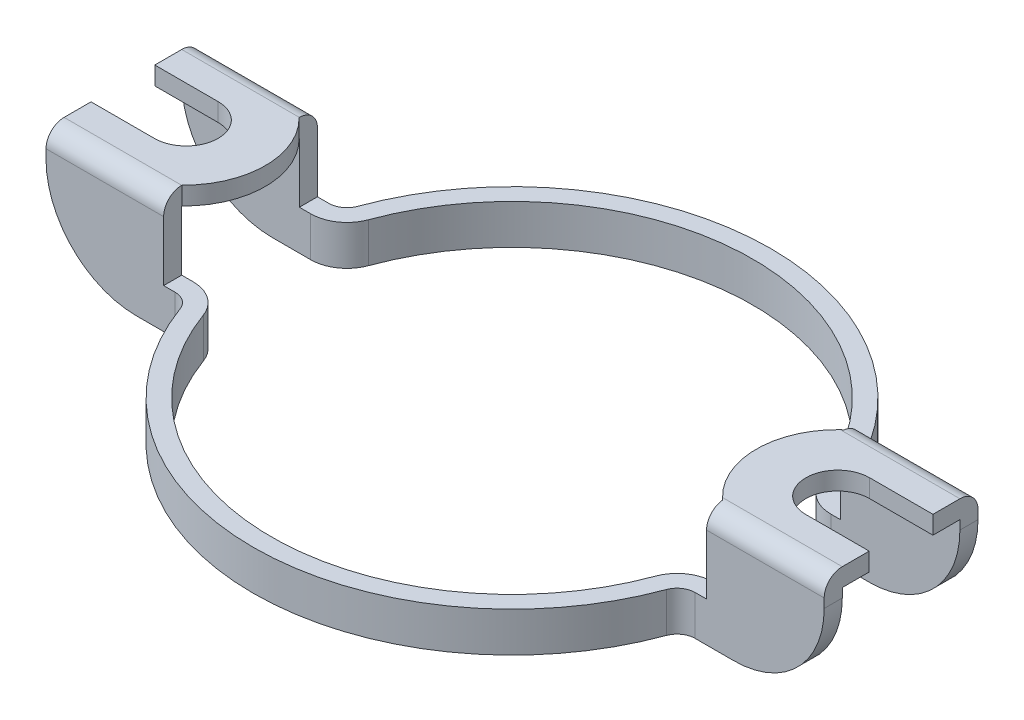
SolidWorks part; units mm, degrees
material "Brass"
ref_plane "Front Plane" through (0, 0, 0) normal (0, 0, 1) x (1, 0, 0)
ref_plane "Top Plane" through (0, 0, 0) normal (0, 1, 0) x (1, 0, 0)
ref_plane "Right Plane" through (0, 0, 0) normal (1, 0, 0) x (0, 0, -1)
sketch "Sketch1" plane through (0, 0, 0) normal (0, 1, 0) x (1, 0, 0)
  line L0 (0, -55) -> (0, 55) construction
  line L1 (-21.5, 4.25) -> (-14.3711, 4.25)
  line L2 (-21.5, 4.25) -> (-21.5, -4.25)
  line L3 (-21.5, -4.25) -> (-14.3711, -4.25)
  line L4 (21.5, 4.25) -> (21.5, -4.25)
  line L5 (-55, 0) -> (55, 0) construction
  line L6 (14.3711, 4.25) -> (21.5, 4.25)
  line L7 (14.3711, -4.25) -> (21.5, -4.25)
  arc A0 (13.4318, 4.9069) -> (-13.4318, 4.9069) centre (0, 0) ccw
  arc A1 (-13.4318, -4.9069) -> (13.4318, -4.9069) centre (0, 0) ccw
  arc A2 (-13.4318, 4.9069) -> (-14.3711, 4.25) centre (-14.3711, 5.25) cw
  arc A3 (14.3711, 4.25) -> (13.4318, 4.9069) centre (14.3711, 5.25) cw
  arc A4 (13.4318, -4.9069) -> (14.3711, -4.25) centre (14.3711, -5.25) cw
  arc A5 (-14.3711, -4.25) -> (-13.4318, -4.9069) centre (-14.3711, -5.25) cw
  point P20 (13.6538, -4.25)
  point P23 (-13.6538, -4.25)
  dimension "D1" = 28.6
  dimension "D6" = 1
  dimension "D2" = 8.5
  dimension "D3" = 43
  dimension "D4" = 21.5
  dimension "D5" = 4.25
extrude "Extrude1" add sketch "Sketch1" against normal blind 6.5
fillet "Fillet1" radius 1 10 edges at (17.9355, 0, -4.25) (13.798, 0, -4.4305) (0, 0, -14.3) (-13.798, 0, -4.4305) (17.9355, 0, 4.25) (13.798, 0, 4.4305) (0, 0, 14.3) (-13.798, 0, 4.4305) (-17.9355, 0, -4.25) (-17.9355, 0, 4.25)
shell "Shell2" thickness 1 removed face at (21.5, -2.431, 0) removed face at (-21.5, -2.431, 0) removed face at (0, -6.5, 0)
sketch "Sketch2" plane through (0, -1, 0) normal (0, -1, 0) x (1, 0, 0)
  circle A0 centre (0, 0) radius 15.25
  dimension "D1" = 30.5
extrude "Extrude2" cut sketch "Sketch2" along normal blind 3.3
sketch "Sketch4" plane through (0, 0, 0) normal (0, 1, 0) x (1, 0, 0)
  line L0 (-3.575, 0) -> (3.575, 0) construction
  line L1 (18, 1.7615) -> (22, 1.7615)
  line L2 (18, -1.7615) -> (22, -1.7615)
  line L3 (22, -1.7615) -> (22, 1.7615)
  line L4 (-18, -1.7615) -> (-22, -1.7615)
  line L5 (-22, -1.7615) -> (-22, 1.7615)
  line L6 (-22, 1.7615) -> (-18, 1.7615)
  line L7 (0, -3.575) -> (0, 3.575) construction
  arc A0 (-18, -1.7615) -> (-18, 1.7615) centre (-18, 0) ccw
  arc A1 (18, 1.7615) -> (18, -1.7615) centre (18, 0) ccw
  dimension "D1" = 36
  dimension "D2" = 18
  dimension "D3" = 4
extrude "Extrude3" cut sketch "Sketch4" against normal through all
sketch "Sketch5" plane through (0, 0, 0) normal (0, 1, 0) x (1, 0, 0)
  line L0 (0, -3.575) -> (0, 3.575) construction
  line L1 (15, -15) -> (-15, -15)
  line L2 (15, -15) -> (15, -3.3541)
  line L3 (15, 15) -> (-15, 15)
  line L4 (-15, 3.2332) -> (-15, 15)
  line L5 (-3.575, 0) -> (3.575, 0) construction
  line L6 (-15, -15) -> (-15, -3.2332)
  line L7 (15, 3.3541) -> (15, 15)
  arc A1 (-15, -3.2332) -> (-15, 3.2332) centre (-18.1299, 0) ccw
  arc A2 (15, 3.3541) -> (15, -3.3541) centre (18, 0) ccw
  dimension "D1" = 30
  dimension "D2" = 9
  dimension "D3" = 15
  dimension "D4" = 30
  dimension "D5" = 15
extrude "Extrude4" cut sketch "Sketch5" against normal up to surface (4.3 mm away) up to face at (0, -4.3, -5.5156)
fillet "Fillet2" radius 5 4 edges at (-21.5, -6.5, 3.75) (-21.5, -6.5, -3.75) (21.5, -6.5, 3.75) (21.5, -6.5, -3.75)
